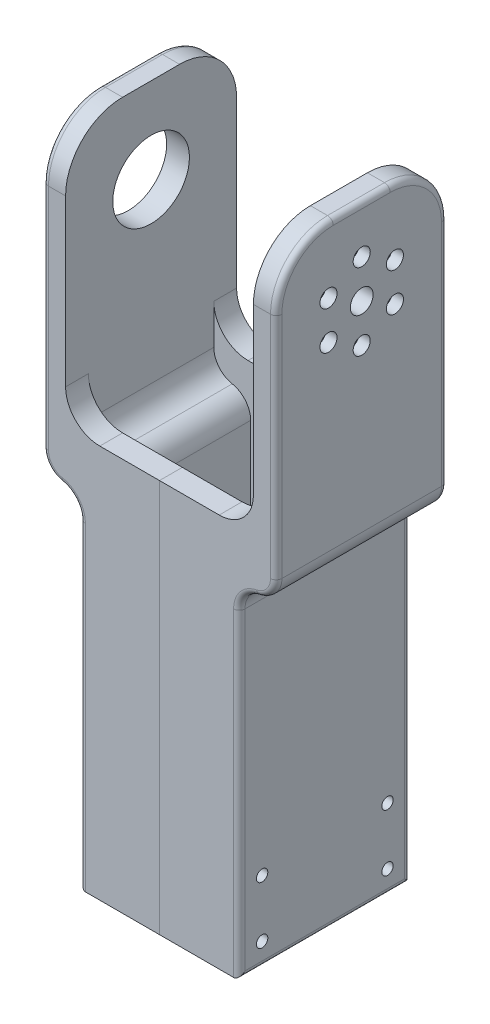
SolidWorks part; units mm, degrees
note: The reader was unsure of these and kept them because the rebuilt part matched: shared geometry of "草图10<2>", "Sketch7<2>".
material "PETG-CF"
ref_plane "前视基准面" through (0, 0, 0) normal (0, 0, 1) x (1, 0, 0)
ref_plane "上视基准面" through (0, 0, 0) normal (0, 1, 0) x (1, 0, 0)
ref_plane "右视基准面" through (0, 0, 0) normal (1, 0, 0) x (0, 0, -1)
other "Configuration Table"
sketch "草图1" plane through (0, 0, 0) normal (1, 0, 0) x (0, 0, -1)
  line L1 (30, -50) -> (-30, -50)
  line L2 (30, -50) -> (30, 50)
  line L3 (30, 50) -> (-30, 50)
  line L4 (-30, -50) -> (-30, 50)
  line L5 (30, -50) -> (-30, 50) construction
  line L6 (30, 50) -> (-30, -50) construction
  point P0 (0, 0)
  dimension "D1" = 100
  dimension "D2" = 60
extrude "凸台-拉伸1" add sketch "草图1" along normal blind 8
sketch "草图2" plane through (8, 0, 0) normal (1, 0, 0) x (0, 0, -1)
  line L1 (30, 50) -> (-30, 50) construction
  circle A12 centre (0, 20) radius 13.45
  point P6 (0, 50)
  point P26 (0, 20)
  dimension "D11" = 26.9
  dimension "D2" = 30
extrude "切除-拉伸1" cut sketch "草图2" against normal through all
sketch "草图3" plane through (8, 0, 0) normal (1, 0, 0) x (0, 0, -1)
  line L0 (-30, 50) -> (-30, -50) construction
  line L1 (-22, -50) -> (-30, -50)
  line L2 (-22, -50) -> (-22, -10)
  line L3 (-22, -10) -> (-30, -10)
  line L4 (-30, -50) -> (-30, -10)
  line L5 (-22, -50) -> (-30, -10) construction
  line L6 (-22, -10) -> (-30, -50) construction
  line L7 (30, -50) -> (22, -50)
  line L8 (30, -50) -> (30, -10)
  line L9 (30, -10) -> (22, -10)
  line L10 (22, -50) -> (22, -10)
  line L11 (30, -50) -> (22, -10) construction
  line L12 (30, -10) -> (22, -50) construction
  line L13 (30, -50) -> (30, 50) construction
  line L14 (30, 50) -> (-30, 50) construction
  line L16 (-30, -50) -> (30, -50) construction
  point P0 (-26, -30)
  point P5 (26, -30)
  dimension "D1" = 60
  dimension "D3" = 60
  dimension "D5" = 8
  dimension "D6" = 8
extrude "凸台-拉伸2" add sketch "草图3" along normal blind 65.9
sketch "草图4" plane through (73.9, 0, 0) normal (1, 0, 0) x (0, 0, -1)
  line L0 (30, -50) -> (-30, 50) construction
  line L1 (30, -50) -> (-30, -50)
  line L2 (30, -50) -> (30, 50)
  line L3 (30, 50) -> (-30, 50)
  line L4 (-30, -50) -> (-30, 50)
  line L5 (30, -50) -> (-30, 50) construction
  line L6 (30, 50) -> (-30, -50) construction
  line L7 (30, 50) -> (-30, 50) construction
  point P0 (0, 0)
extrude "凸台-拉伸3" add sketch "草图4" along normal blind 8
sketch "草图10" plane through (81.9, 0, 0) normal (1, 0, 0) x (0, 0, -1)
  circle A0 centre (0, 20) radius 4
  circle A1 centre (0, 20) radius 13.5 construction
  circle A2 centre (0, 33.5) radius 1.6
  circle A3 centre (11.6913, 26.75) radius 1.6
  circle A4 centre (11.6913, 13.25) radius 1.6
  circle A5 centre (0, 6.5) radius 1.6
  circle A6 centre (-11.6913, 13.25) radius 1.6
  circle A7 centre (-11.6913, 26.75) radius 1.6
  point P18 (0, 20)
  dimension "D1" = 8
  dimension "D2" = 27
  dimension "D3" = 3.2
  dimension "D4" = 6
extrude "切除-拉伸2" cut sketch "草图10" against normal up to next
sketch "草图15" plane through (73.9, 0, 0) normal (-1, 0, 0) x (0, 0, 1)
  circle A0 centre (0, 20) radius 18
  dimension "D1" = 36
extrude "凸台-拉伸4" add sketch "草图15" along normal blind 9.8
sketch "草图12" plane through (81.9, 0, 0) normal (1, 0, 0) x (0, 0, -1)
  circle A0 centre (0, 33.45) radius 3
  circle A1 centre (0, 20) radius 13.45 construction
  circle A2 centre (11.648, 26.725) radius 3
  circle A3 centre (11.648, 13.275) radius 3
  circle A4 centre (0, 6.55) radius 3
  circle A5 centre (-11.648, 13.275) radius 3
  circle A6 centre (-11.648, 26.725) radius 3
  point P16 (0, 20)
  dimension "D1" = 6
  dimension "D2" = 6
extrude "切除-拉伸4" cut sketch "草图12" against normal blind 4
extrude "切除-拉伸7" cut sketch "草图10<2>" against normal up to next
sketch "草图10<2>" plane through (81.9, 0, 0) normal (1, 0, 0) x (0, 0, -1) same geometry as "草图10"
sketch "Sketch1" plane through (0, 0, -30) normal (0, 0, -1) x (-1, 0, 0)
  line L0 (-8, -10) -> (-8, 50) construction
  line L1 (-73.9, -10) -> (-8, -10)
  line L2 (-73.9, -10) -> (-73.9, -40)
  line L3 (-73.9, -40) -> (-8, -40)
  line L4 (-8, -10) -> (-8, -40)
  line L5 (-73.9, -10) -> (-8, -10) construction
  line L6 (-73.9, -10) -> (-73.9, 50) construction
  dimension "D1" = 30
extrude "Cut-Extrude1" cut sketch "Sketch1" against normal through all
sketch "Sketch2" plane through (0, 0, 30) normal (0, 0, 1) x (1, 0, 0)
  line L1 (12.95, -58) -> (20.95, -58)
  line L2 (12.95, -58) -> (12.95, -178)
  line L3 (12.95, -178) -> (20.95, -178)
  line L4 (20.95, -58) -> (20.95, -178)
  line L6 (68.95, -58) -> (60.95, -58)
  line L7 (68.95, -58) -> (68.95, -178)
  line L8 (68.95, -178) -> (60.95, -178)
  line L9 (60.95, -58) -> (60.95, -178)
  line L12 (20.95, -50) -> (60.95, -50)
  line L13 (0, -50) -> (20.95, -50)
  line L14 (0, -50) -> (0, -58)
  line L15 (0, -58) -> (20.95, -58)
  line L16 (20.95, -50) -> (20.95, -58)
  line L17 (81.9, -50) -> (60.95, -50)
  line L18 (81.9, -50) -> (81.9, -58)
  line L19 (81.9, -58) -> (60.95, -58)
  line L20 (60.95, -50) -> (60.95, -58)
  line L21 (73.9, -40) -> (8, -40) construction
  point P15 (40.95, -40)
  point P22 (40.95, -50)
  line M7 (0, -50) -> (81.9, -50)
  dimension "D1" = 8
  dimension "D2" = 8
  dimension "D3" = 120
  dimension "D4" = 8
  dimension "D5" = 8
  dimension "D6" = 40
extrude "Boss-Extrude3" add sketch "Sketch2" along direction (0, 0, 1) on the side against the normal up to surface (60 mm away) contours L4 L1 L2 L3 | L16 L13 L14 L15 L1 M7 | L6 L9 L8 L7 | L20 L6 L19 L18 L17 M7
fillet "Fillet1" radius 12 4 edges at (8, -40, -26) (8, -40, 26) (73.9, -40, 26) (73.9, -40, -26)
fillet "Fillet3" radius 8 4 edges at (8, -50, 0) (73.9, -50, 0) (68.95, -58, 0) (12.95, -58, 0)
fillet "Fillet4" radius 8 10 edges at (18.475, -50, -22) (16, -50, 0) (18.475, -50, 22) (20.95, -50, 0) (63.425, -50, 22) (65.9, -50, 0) (63.425, -50, -22) (60.95, -50, 0) (81.9, -58, 0) (0, -58, 0)
sketch "Sketch3" plane through (20.95, 0, 0) normal (1, 0, 0) x (0, 0, -1)
  line L0 (30, -178) -> (-30, -178) construction
  line L1 (-30, -50) -> (-22, -50)
  line L2 (-30, -50) -> (-30, -178)
  line L3 (-30, -178) -> (-22, -178)
  line L4 (-22, -50) -> (-22, -178)
  line L6 (30, -178) -> (22, -178)
  line L7 (30, -178) -> (30, -50)
  line L8 (30, -50) -> (22, -50)
  line L9 (22, -178) -> (22, -50)
  line L10 (-22, -50) -> (-30, -50) construction
  line L12 (30, -50) -> (22, -50) construction
  dimension "D1" = 8
  dimension "D2" = 8
extrude "Boss-Extrude4" add sketch "Sketch3" along normal up to surface (40 mm away)
fillet "Fillet5" radius 20 4 edges at (77.9, 50, 30) (4, 50, 30) (4, 50, -30) (77.9, 50, -30)
fillet "Fillet6" radius 2 24 edges at (70.7775, -60.9108, 30) (80.0725, -55.3826, 30) (81.9, -10.1467, 30) (81.9, 44.1421, 24.1421) (81.9, 50, 0) (81.9, 44.1421, -24.1421) (81.9, -10.1467, -30) (80.0725, -55.3826, -30) (70.7775, -60.9108, -30) (11.1225, -60.9108, -30) (1.8275, -55.3826, -30) (0, -10.1467, -30) (0, 44.1421, -24.1421) (0, 50, 0) (0, 44.1421, 24.1421) (0, -10.1467, 30) (1.8275, -55.3826, 30) (11.1225, -60.9108, 30) (68.95, -178, 0) (68.95, -122, -30) (68.95, -122, 30) (12.95, -178, 0) (12.95, -122, 30) (12.95, -122, -30)
sketch "Sketch7" plane through (68.95, 0, 0) normal (1, 0, 0) x (0, 0, -1)
  line L0 (30, -178) -> (30, -66) construction
  line L1 (-22, -150) -> (22, -150) construction
  line L2 (-22, -150) -> (-22, -170) construction
  line L3 (-22, -170) -> (22, -170) construction
  line L4 (22, -150) -> (22, -170) construction
  line L5 (-30, -66) -> (-30, -178) construction
  line L6 (30, -178) -> (-30, -178) construction
  line L7 (-22, -160) -> (22, -160) construction
  line L8 (0, -170) -> (0, -150) construction
  circle A0 centre (-22, -150) radius 2
  circle A1 centre (22, -150) radius 2
  circle A2 centre (22, -170) radius 2
  circle A3 centre (-22, -170) radius 2
  dimension "D5" = 4
  dimension "D1" = 8
  dimension "D2" = 8
  dimension "D3" = 8
  dimension "D4" = 20
extrude "Cut-Extrude2" cut sketch "Sketch7" against normal blind 8
extrude "Cut-Extrude3" cut sketch "Sketch7<2>" along normal blind 8 from surface at -56 starting at face at (12.95, -121, 0)
sketch "Sketch7<2>" plane through (68.95, 0, 0) normal (1, 0, 0) x (0, 0, -1) same geometry as "Sketch7"
ref_plane "基准面1" through (40.95, 0, 0) normal (1, 0, 0) x (0, 0, -1)
split "分割1" trim tools "基准面1" bodies to split 133 resulting bodies 125 126
